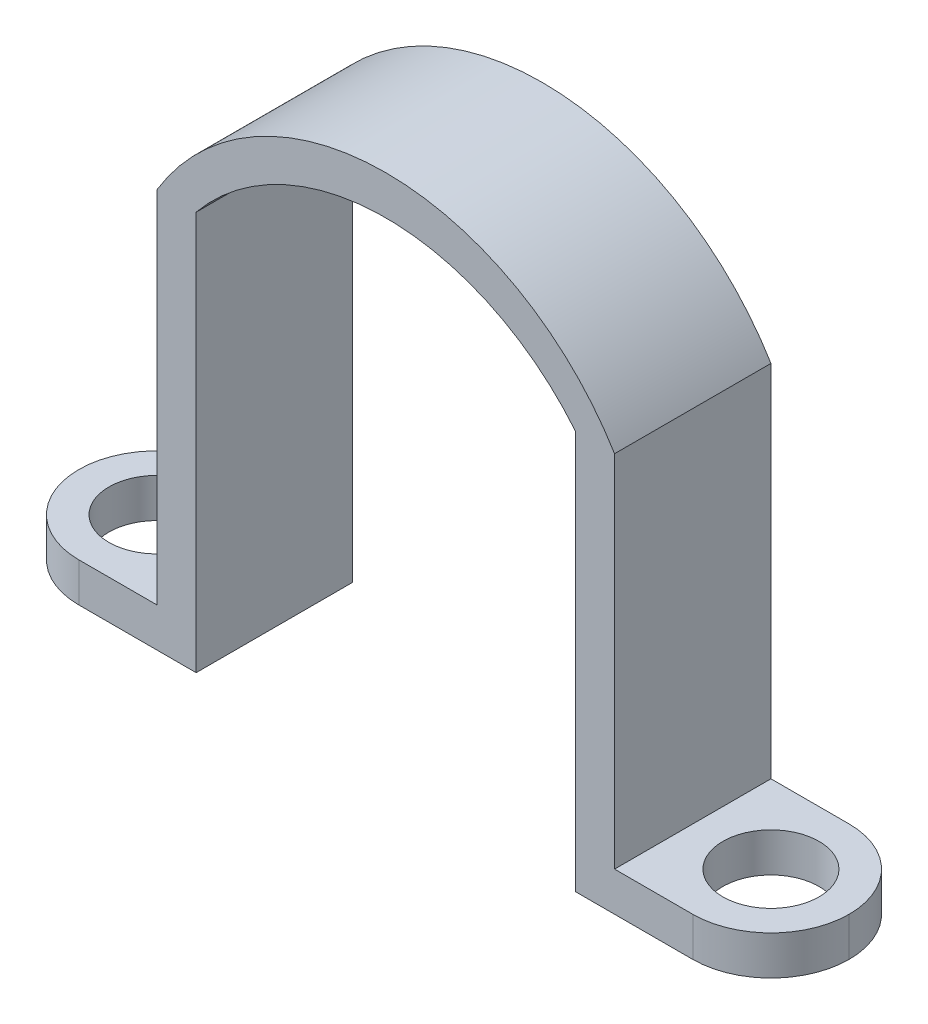
SolidWorks part; units mm, degrees
ref_plane "Front Plane" through (0, 0, 0) normal (0, 0, 1) x (1, 0, 0)
ref_plane "Top Plane" through (0, 0, 0) normal (0, 1, 0) x (1, 0, 0)
ref_plane "Right Plane" through (0, 0, 0) normal (1, 0, 0) x (0, 0, -1)
sketch "Sketch1" plane through (0, 0, 0) normal (0, 0, 1) x (1, 0, 0)
  line L0 (18.669, -23.47) -> (12.319, -23.47)
  line L1 (12.319, -23.47) -> (12.319, -10.516)
  line L2 (0, -10.516) -> (0, -23.47)
  line L3 (0, -23.47) -> (-6.35, -23.47)
  line L4 (18.669, -22.2) -> (13.589, -22.2)
  line L5 (13.589, -22.2) -> (13.589, -10.516)
  line L6 (-1.27, -10.516) -> (-1.27, -22.2)
  line L7 (-1.27, -22.2) -> (-6.35, -22.2)
  line L8 (-6.35, -23.47) -> (-6.35, -22.2)
  line L9 (18.669, -23.47) -> (18.669, -22.2)
  line L12 (0, -2.794) -> (0, 2.794) construction
  arc A0 (12.319, -10.516) -> (0, -10.516) centre (6.1595, -15.5497) ccw
  arc A2 (-1.94, -15.43) -> (14.14, -15.43) centre (6.1, -15.43) ccw construction
  arc A3 (13.589, -10.516) -> (-1.27, -10.516) centre (6.1595, -15.0057) ccw
  point P5 (6.1595, -6.325)
  point P22 (6.1595, -7.595)
  dimension "D2" = 1.27
  dimension "D1" = 1.27
  dimension "D3" = 1.27
  dimension "D4" = 5.08
  dimension "D5" = 12.319
  dimension "D6" = 12.954
  dimension "D7" = 2.921
  dimension "D8" = 1.27
extrude "Boss-Extrude1" add sketch "Sketch1" along normal blind 5.08
fillet "Fillet1" radius 2.54 4 edges at (-6.35, -22.835, 0) (-6.35, -22.835, 5.08) (18.669, -22.835, 0) (18.669, -22.835, 5.08)
sketch "Sketch2" plane through (0, -22.2, 0) normal (0, 1, 0) x (1, 0, 0)
  circle A0 centre (16.129, -2.54) radius 1.5625
  arc A1 (18.669, -2.54) -> (16.129, 0) centre (16.129, -2.54) ccw construction
  circle A3 centre (55.0473, -38.3624) radius 1.5625 construction
  circle A4 centre (-3.81, -2.54) radius 1.5625
  arc A5 (-3.81, 0) -> (-6.35, -2.54) centre (-3.81, -2.54) ccw construction
extrude "Cut-Extrude1" cut sketch "Sketch2" against normal through all
